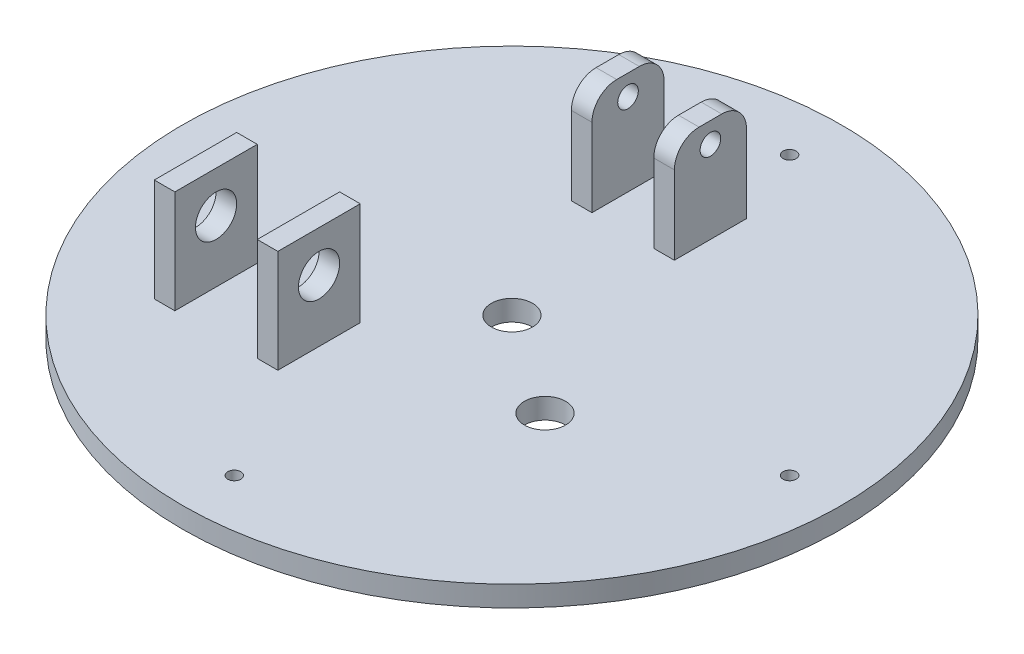
SolidWorks part; units mm, degrees
material "6061 Alloy"
ref_plane "Front Plane" through (0, 0, 0) normal (0, 0, 1) x (1, 0, 0)
ref_plane "Top Plane" through (0, 0, 0) normal (0, 1, 0) x (1, 0, 0)
ref_plane "Right Plane" through (0, 0, 0) normal (1, 0, 0) x (0, 0, -1)
sketch "Sketch1" plane through (0, 0, 0) normal (0, 1, 0) x (1, 0, 0)
  circle A0 centre (0, 0) radius 101.6
  dimension "D1" = 203.2
extrude "Boss-Extrude1" add sketch "Sketch1" along normal blind 6.35
sketch "Sketch2" plane through (0, 0, 0) normal (0, -1, 0) x (1, 0, 0)
  circle A0 centre (0, 0) radius 6.35
  dimension "D1" = 12.7
extrude "Cut-Extrude1" cut sketch "Sketch2" against normal through all
sketch "Sketch3" plane through (0, 6.35, 0) normal (0, 1, 0) x (1, 0, 0)
  line L0 (-53.1127, -38.1) -> (-27.7127, -38.1) construction
  line L1 (-59.4627, -25.4) -> (-53.1127, -25.4)
  line L2 (-59.4627, -25.4) -> (-59.4627, -50.8)
  line L3 (-59.4627, -50.8) -> (-53.1127, -50.8)
  line L4 (-53.1127, -25.4) -> (-53.1127, -50.8)
  line L5 (-27.7127, -25.4) -> (-21.3627, -25.4)
  line L6 (-27.7127, -25.4) -> (-27.7127, -50.8)
  line L7 (-27.7127, -50.8) -> (-21.3627, -50.8)
  line L8 (-21.3627, -25.4) -> (-21.3627, -50.8)
  point P10 (-40.4127, -38.1)
  dimension "D1" = 40.4127
  dimension "D2" = 6.35
  dimension "D3" = 38.1
  dimension "D4" = 25.4
  dimension "D5" = 25.4
extrude "Boss-Extrude2" add sketch "Sketch3" along normal blind 31.75
sketch "Sketch4" plane through (-21.3627, 0, 0) normal (1, 0, 0) x (0, 0, -1)
  line L0 (-38.1, 38.1) -> (-38.1, 25.4) construction
  line L1 (-50.8, 38.1) -> (-25.4, 38.1) construction
  circle A0 centre (-38.1, 25.4) radius 6.35
  dimension "D1" = 12.7
  dimension "D2" = 12.7
extrude "Cut-Extrude2" cut sketch "Sketch4" against normal up to surface (38.1 mm away) up to face at (-59.4627, 22.225, 38.1)
sketch "Sketch5" plane through (0, 6.35, 0) normal (0, 1, 0) x (1, 0, 0)
  line L0 (-15.0127, 50.8) -> (4.0373, 50.8) construction
  line L2 (-21.3627, 39.6875) -> (-15.0127, 39.6875)
  line L3 (-21.3627, 39.6875) -> (-21.3627, 61.9125)
  line L4 (-21.3627, 61.9125) -> (-15.0127, 61.9125)
  line L5 (-15.0127, 39.6875) -> (-15.0127, 61.9125)
  line L6 (4.0373, 61.9125) -> (10.3873, 61.9125)
  line L7 (4.0373, 61.9125) -> (4.0373, 39.6875)
  line L8 (4.0373, 39.6875) -> (10.3873, 39.6875)
  line L9 (10.3873, 61.9125) -> (10.3873, 39.6875)
  point P10 (-5.4877, 50.8)
  dimension "D1" = 22.225
  dimension "D2" = 6.35
  dimension "D3" = 19.05
  dimension "D4" = 34.925
  dimension "D5" = 88.9
extrude "Boss-Extrude3" add sketch "Sketch5" along normal blind 31.75
sketch "Sketch6" plane through (-21.3627, 0, 0) normal (-1, 0, 0) x (0, 0, 1)
  line L0 (-50.8, 38.1) -> (-50.8, 31.75) construction
  line L1 (-61.9125, 38.1) -> (-39.6875, 38.1) construction
  circle A0 centre (-50.8, 31.75) radius 3.175
  dimension "D1" = 6.35
  dimension "D2" = 6.35
extrude "Cut-Extrude3" cut sketch "Sketch6" against normal up to surface (31.75 mm away) up to face at (10.3873, 22.225, -50.8)
hole_wizard "#10-32 Tapped Hole1" positions "Sketch8" profile "Sketch7" tap size "#10-32" standard "ANSI Inch"
sketch "Sketch8" plane through (0, 0, 0) normal (0, -1, 0) x (-1, 0, 0)
  line L1 (85.5998, 0) -> (0, 85.5998)
  line L2 (85.5998, 0) -> (0, -85.5998)
  line L3 (0, 85.5998) -> (-85.5998, 0)
  line L4 (0, -85.5998) -> (-85.5998, 0)
  line L5 (85.5998, 0) -> (-85.5998, 0) construction
  line L6 (0, 85.5998) -> (0, -85.5998) construction
  point P252 (0, 0)
  point P331 (0, -85.5998)
  point P333 (-85.5998, 0)
  point P335 (0, 85.5998)
  point P337 (85.5998, 0)
  dimension "D1" = 121.0564
sketch "Sketch7" plane through (0, 0, 0) normal (1, 0, 0) x (0, 0, -1)
  line L0 (0, 0) -> (0, 13.2428)
  line L1 (0, 13.2428) -> (2.0193, 12.0294)
  line L2 (2.0193, 12.0294) -> (2.0193, 0)
  line L5 (2.0193, 0) -> (0, 0)
  line L10 (0, 13.2428) -> (-2.0193, 12.0294) construction
  line L11 (0, -6.35) -> (0, 107.95) construction
  dimension "Tap Drill Dia." = 4.0386
  dimension "Tap Drill Depth" = 12.0294
  dimension "Drill Angle" = 118
fillet "Fillet1" radius 7.62 4 edges at (7.2123, 38.1, -39.6875) (-18.1877, 38.1, -39.6875) (-18.1877, 38.1, -61.9125) (7.2123, 38.1, -61.9125)
sketch "Sketch9" plane through (0, 6.35, 0) normal (0, 1, 0) x (1, 0, 0)
  line L0 (0, 0) -> (84.2496, -56.7852) construction
  line L1 (0, 0) -> (31.2671, -21.0744) construction
  circle A0 centre (0, 0) radius 101.6 construction
  circle A1 centre (31.2671, -21.0744) radius 6.35
  dimension "D2" = 12.7
  dimension "D1" = 37.7063
extrude "Cut-Extrude4" cut sketch "Sketch9" against normal through all
